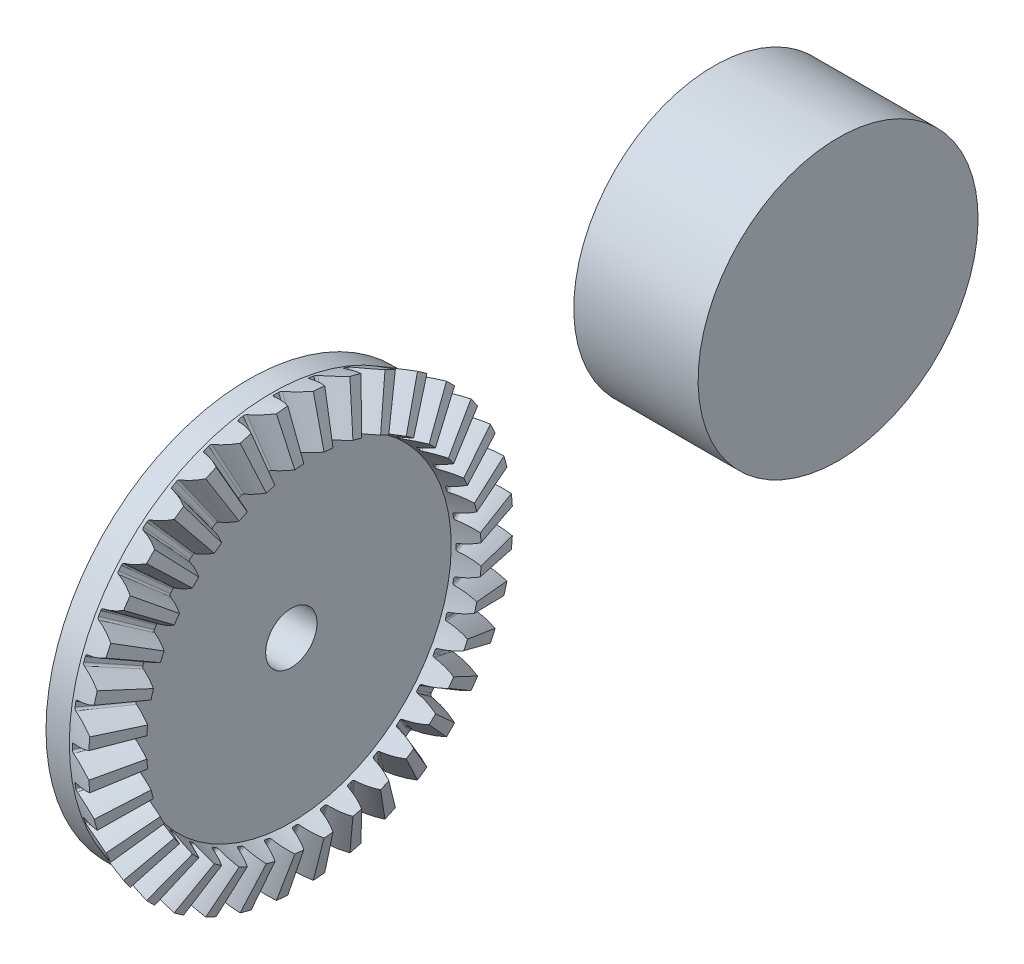
SolidWorks part; units mm, degrees
revolve "Base-Revolve" add sketch "BasProSke" angle 360 about L0 other way angle 5
sketch "BasProSke" plane through (0, 0, 0) normal (0, 1, 0) x (1, 0, 0)
  line L0 (-10, 0) -> (60, 0) construction
  line L1 (0, 0) -> (0, 8.684)
  line L2 (0, 0) -> (0.8323, 0)
  line L3 (0.8323, 0) -> (0.8323, 6.8532)
  line L4 (3.948, 0) -> (-9.0794, 39.0823) construction
  line L5 (0, 8.684) -> (1.2284, 9.0935)
  line L6 (3.948, 0) -> (-23.6442, 92.2592) construction
  line L7 (3.948, 0) -> (0, 8.684) construction
  line L8 (1.2284, 9.0935) -> (1.8018, 7.1764)
  line L9 (1.8018, 7.1764) -> (0.8323, 6.8532)
  line L10 (0.948, 9) -> (-11.0363, 9) construction
  dimension "D1" = 17.368
  dimension "D2" = 3.948
  dimension "D3" = 9.4868
  dimension "D4" = 1.784
ref_plane "Plane1" through (0, 0, 0) normal (0, 0, 1) x (1, 0, 0)
ref_plane "Plane2" through (0, 0, 0) normal (0, 1, 0) x (1, 0, 0)
ref_plane "Plane3" through (0, 0, 0) normal (1, 0, 0) x (0, 0, -1)
other "Configuration Table"
sketch "HoldingSke" plane through (0, 0, 0) normal (0, 1, 0) x (1, 0, 0)
  line L0 (0, 0) -> (1.618, -1.1756)
  line L1 (-15, 0) -> (100, 0) construction
  line L2 (0, 0) -> (-122.6628, 25.2748)
  line L3 (0, 0) -> (-11.863, 4.5341)
  line L4 (0, 0) -> (6.9867, 5.0761)
  line L5 (0, 0) -> (-2.8109, -1.0484)
  line L6 (0, 0) -> (-10.5278, -7.1032)
  line L7 (-122.6628, 25.2748) -> (-122.6331, 29.2228)
  line L8 (-76.2, 0.5) -> (-75.9, 0.5)
  line L9 (-71.009, 38.7566) -> (-53.1078, 45.2721)
  line L10 (-76.2, 71.12) -> (104.1128, 71.12)
  line L11 (0, 0) -> (-1.5, 0)
  line L12 (-76.2, 101.6) -> (-76.181, 101.6)
  line L13 (24.9733, 27.94) -> (52.9546, 28.2287)
  line L14 (24.9733, 27.94) -> (24.9743, 27.94)
  line L15 (24.9733, 27.94) -> (100.3893, 30.0425)
  line L16 (-122.6628, 25.2748) -> (3.6233, -1.5681)
  circle A0 centre (0, 0) radius 1
  circle A1 centre (0, 0) radius 3
  circle A2 centre (0, 0) radius 3
  circle A3 centre (0, 0) radius 1
  dimension "Num_teeth" = 36
  dimension "Pitch_radius" = 180.3128
  dimension "Width" = 1.5
ref_plane "ToothPln" through (0.6142, 8.8887, 0) normal (-0.3162, 0.9487, 0) x (0, 0, -1)
ref_plane "ToothPln2" through (0.3948, -1.1844, 0) normal (-0.3162, 0.9487, 0) x (0, 0, 1)
sketch "TooCutSke" plane through (0.6142, 8.8887, 0) normal (-0.3162, 0.9487, 0) x (0, 0, -1)
  line L2 (0, 8.6481) -> (144.0891, -1638.2981) construction
  line L3 (0, 8.6481) -> (78.8921, -1755.5054) construction
  line L4 (0, -15.621) -> (0, 105.791) construction
  line L6 (-24.765, -0.6474) -> (21.082, -0.6474) construction
  line L7 (0.7844, -0.3176) -> (0.4017, -0.3347) construction
  arc A0 (-0.6442, -0.8114) -> (0.6442, -0.8114) centre (0, 8.6481) ccw
  arc A1 (-0.094, 0.4481) -> (0.094, 0.4481) centre (0, 8.6481) ccw
  circle A2 centre (0, 8.6481) radius 9 construction
  circle A3 centre (0, 8.6481) radius 8.4572 construction
  arc A4 (0.1883, 0.3711) -> (0.094, 0.4481) centre (0.0951, 0.3531) ccw
  arc A5 (0.1883, 0.3711) -> (0.6442, -0.8114) centre (3.7229, 1.0544) ccw
  arc A6 (-0.6442, -0.8114) -> (-0.1883, 0.3711) centre (-3.7229, 1.0544) ccw
  arc A7 (-0.094, 0.4481) -> (-0.1883, 0.3711) centre (-0.0951, 0.3531) ccw
  ellipse E0 centre (0, 2.2282) end of major axis (9.0935, 2.2282) minor radius 2.8756 construction
sketch "TooCutSke2" plane through (0.3948, -1.1844, 0) normal (-0.3162, 0.9487, 0) x (0, 0, 1)
  line L0 (0, 0) -> (0, 68.072) construction
  line L2 (21.082, 2.7461) -> (-20.32, 2.7461) construction
  circle A0 centre (0, 3.7454) radius 0.0127
  ellipse E1 centre (0, 0) end of major axis (-8.684, 0) minor radius 2.7461 construction
loft "ToothCut" cut profiles "TooCutSke2", "TooCutSke"
pattern_circular "TeethCuts" count 36 every 10 about axis through (-10, 0, 0) along (1, 0, 0) of "ToothCut"
sketch "HubSke" plane through (0, 0, 0) normal (-1, 0, 0) x (0, 0, 1)
  circle A0 centre (0, 0) radius 8.684
  circle A1 centre (0, 0) radius 8.684 construction
extrude "Hub" add sketch "HubSke" along normal blind 1
sketch "草图1" plane through (0.8323, 0, 0) normal (1, 0, 0) x (0, 0, -1)
  circle A0 centre (18.1074, 6.1763) radius 6
  dimension "D1" = 12
extrude "凸台-拉伸1" add sketch "草图1" along normal up to surface (5.329 mm away)
sketch "BorSke" plane through (0, 0, 0) normal (1, 0, 0) x (0, 0, -1)
  circle A0 centre (0, 0) radius 1.1
  dimension "Diameter" = 2.2
extrude "Bore" cut sketch "BorSke" along normal mid plane 7.8962
sketch "KeySke" plane through (0, 0, 0) normal (1, 0, 0) x (0, 0, -1)
  line L0 (-0.4, 0) -> (-0.4, 1.3)
  line L1 (-0.4, 1.3) -> (0.4, 1.3)
  line L2 (0.4, 1.3) -> (0.4, 0)
  line L3 (0, 0) -> (0, 34) construction
  line L4 (-0.4, 0) -> (0.4, 0)
  dimension "Offset" = 1.3
extrude "Keyway" [suppressed] cut sketch "KeySke" along normal mid plane 7.8962
pattern_circular "Keyway2" [suppressed] count 2 every 90 about axis through (-10, 0, 0) along (1, 0, 0) reverse direction yes
equation "' \"Module@HoldingSke\" = 6.35"
equation "' \"Num_teeth@HoldingSke\" = 20"
equation "' \"Mating_teeth@HoldingSke\" = 12"
equation "' \"Ap@HoldingSke\" =  20"
equation "' \"Ap@HoldingSke\" = 20"
equation "' \"Width@HoldingSke\" = 0.5 * 25.4"
equation "' \"Hub_dia@HoldingSke\"= 2 * 25.4"
equation "' \"Hub_dia@HoldingSke\" = 2 * 25.4"
equation "' \"Mounting_dist@HoldingSke\" = 3 * 25.4"
equation "' \"Bore@HoldingSke\" = 19"
equation "' \"T_dim@HoldingSke\" = 0.1 * 25.4"
equation "' \"Width@KeySke\" = 0.25 * 25.4"
equation "' \"Show_teeth@HoldingSke\" = 100"
equation "' \"Backlash@HoldingSke\" = 0.009 * 25.4"
equation "' \"Addendum_fac@HoldingSke\" = 1.0"
equation "' \"Dedendum_fac@HoldingSke\" = 1.188"
equation "' \"Dedendum_add@HoldingSke\" = 0.002 * 25.4"
equation "' \"Clearance_fac@HoldingSke\" = 0.188"
equation "\"Pitch@HoldingSke\" = 1 / \"Module@HoldingSke\""
equation " \"Addendum_fac@HoldingSke\" = 0.54 + 0.46 / (\"Num_teeth@HoldingSke\" /  \"Mating_teeth@HoldingSke\" ) ^ 2"
equation "' \"Addendum_fac@HoldingSke\" = 2 - (0.54 + 0.46 / (\"Mating_teeth@HoldingSke\" /  \"Num_teeth@HoldingSke\" ) ^ 2)"
equation "\"Dedendum_fac@HoldingSke\" = 2.188 - \"Addendum_fac@HoldingSke\""
equation "\"Pitch_rad@BasProSke\" = \"Num_teeth@HoldingSke\" / \"Pitch@HoldingSke\" / 2"
equation "\"Pitch_ang@BasProSke\" = atn(\"Num_teeth@HoldingSke\" / \"Mating_teeth@HoldingSke\") * (180 / 3.14159265)"
equation "\"Addendum@BasProSke\" = \"Addendum_fac@HoldingSke\" / \"Pitch@HoldingSke\""
equation "\"Dedendum_plus@BasProSke\" = (\"Dedendum_fac@HoldingSke\" / \"Pitch@HoldingSke\" + \"Dedendum_add@HoldingSke\") * 1.25"
equation "\"Radius@TooCutSke\" = ((\"Num_teeth@HoldingSke\" + 2 * \"Addendum_fac@HoldingSke\") / \"Pitch@HoldingSke\" ) / 2"
equation "\"Overcut_dia@TooCutSke\" =  1.02 * (\"Num_teeth@HoldingSke\" + 2 * \"Addendum_fac@HoldingSke\") / \"Pitch@HoldingSke\""
equation "\"Pitch_dia@TooCutSke\" = \"Num_teeth@HoldingSke\" / \"Pitch@HoldingSke\""
equation "\"Base_dia@TooCutSke\" = \"Num_teeth@HoldingSke\" / \"Pitch@HoldingSke\" * cos((\"Ap@HoldingSke\"  * 3.14159265 / 180))"
equation "'  \"Root_dia@TooCutSke\" =  (\"Num_teeth@HoldingSke\" + 2) / \"Pitch@HoldingSke\" - 2 * (\"Addendum_fac@HoldingSke\" + \"Dedendum_fac@HoldingSke\") / \"Pitch@HoldingSke\" - \"Dedendum_add@HoldingSke\" * 2"
equation "'  \"Root_dia@TooCutSke\" = (\"Num_teeth@HoldingSke\" + 2) / \"Pitch@HoldingSke\" - 2 * (\"Addendum_fac@HoldingSke\" + \"Dedendum_fac@HoldingSke\") / \"Pitch@HoldingSke\" - \"Dedendum_add@HoldingSke\" * 2"
equation "\"Root_dia@TooCutSke\" =  \"Num_teeth@HoldingSke\" / \"Pitch@HoldingSke\" -  2 * \"Dedendum_fac@HoldingSke\" / \"Pitch@HoldingSke\" - \"Dedendum_add@HoldingSke\" * 2"
equation "\"Half_ang@TooCutSke\" = 180 / \"Num_teeth@HoldingSke\""
equation "\"Half_CT@TooCutSke\" = \"Num_teeth@HoldingSke\" / \"Pitch@HoldingSke\" * sin((3.14159265 / 2 / \"Num_teeth@HoldingSke\")) / 2 - 2 * \"Backlash@HoldingSke\" / 4"
equation "\"Flank_rad@TooCutSke\" = \"Num_teeth@HoldingSke\" / \"Pitch@HoldingSke\" / 5"
equation "\"Root_fillet@TooCutSke\" = \"Clearance_fac@HoldingSke\" / \"Pitch@HoldingSke\" + \"Dedendum_add@HoldingSke\""
equation "\"Offset@ToothPln2\"  = \"Num_teeth@HoldingSke\" / \"Pitch@HoldingSke\" / 2 / sin(atn(\"Num_teeth@HoldingSke\" / \"Mating_teeth@HoldingSke\"))"
equation "\"Dedendum_plus@TooCutSke2\" = \"Dedendum_plus@BasProSke\""
equation "\"MHD@HoldingSke\" = \"Num_teeth@HoldingSke\" / \"Pitch@HoldingSke\" - 2 * \"Dedendum_plus@BasProSke\" * cos(atn(\"Num_teeth@HoldingSke\" / \"Mating_teeth@HoldingSke\"))"
equation "\"MBD@HoldingSke\" = \"Num_teeth@HoldingSke\" / \"Pitch@HoldingSke\" - 2 * \"Dedendum_plus@BasProSke\" * cos(atn(\"Num_teeth@HoldingSke\" / \"Mating_teeth@HoldingSke\")) - 0.002 * 25.4"
equation "\"MnMD@HoldingSke\" =  \"Num_teeth@HoldingSke\" / \"Pitch@HoldingSke\" / 2 / (\"Num_teeth@HoldingSke\" / \"Mating_teeth@HoldingSke\") + \"Dedendum_plus@BasProSke\" * sin(atn(\"Num_teeth@HoldingSke\" / \"Mating_teeth@HoldingSke\"))"
equation "\"OAL@HoldingSke\" = \"MnMD@HoldingSke\""
equation "\"MHD@HoldingSke\" = ((sgn( \"MHD@HoldingSke\" - \"Hub_dia@HoldingSke\" )-1)*( \"MHD@HoldingSke\" - \"Hub_dia@HoldingSke\" ))/-2+ \"Hub_dia@HoldingSke\""
equation "\"MBD@HoldingSke\" = ((sgn( \"MBD@HoldingSke\" - \"Bore@HoldingSke\" )-1)*( \"MBD@HoldingSke\" - \"Bore@HoldingSke\" ))/-2+ \"Bore@HoldingSke\""
equation "\"Face_wid@BasProSke\" = ((sgn( \"Face_wid@BasProSke\" - \"Offset@ToothPln2\" * 0.9)-1)*( \"Face_wid@BasProSke\" - \"Offset@ToothPln2\" * 0.9))/-2+ \"Offset@ToothPln2\" * 0.9"
equation "\"OAL@HoldingSke\" = ((sgn( \"OAL@HoldingSke\" - \"Mounting_dist@HoldingSke\" )+1)*( \"OAL@HoldingSke\" - \"Mounting_dist@HoldingSke\" ))/2 + \"Mounting_dist@HoldingSke\" + 0.000002 * 25.4"
equation "\"Num_teeth@TeethCuts\" = int( \"Show_teeth@HoldingSke\" ) + 1"
equation "\"Num_teeth@TeethCuts\" = ((sgn( \"Num_teeth@TeethCuts\" - \"Num_teeth@HoldingSke\" )-1)*( \"Num_teeth@TeethCuts\" - \"Num_teeth@HoldingSke\" ))/-2+ \"Num_teeth@HoldingSke\""
equation "\"Num_teeth@TeethCuts\" = ((sgn( \"Num_teeth@TeethCuts\" - 2.0)+1)*( \"Num_teeth@TeethCuts\" - 2.0))/2 +2.0"
equation "\"Angle@TeethCuts\" = 360.0 / \"Num_teeth@HoldingSke\""
equation "\"D1@Bore\" = \"OAL@HoldingSke\" * 2.0"
equation "\"D1@Keyway\" = \"OAL@HoldingSke\" * 2.0"
equation "\"Offset@KeySke\" = \"T_dim@HoldingSke\" + \"MBD@HoldingSke\" / 2.0"
